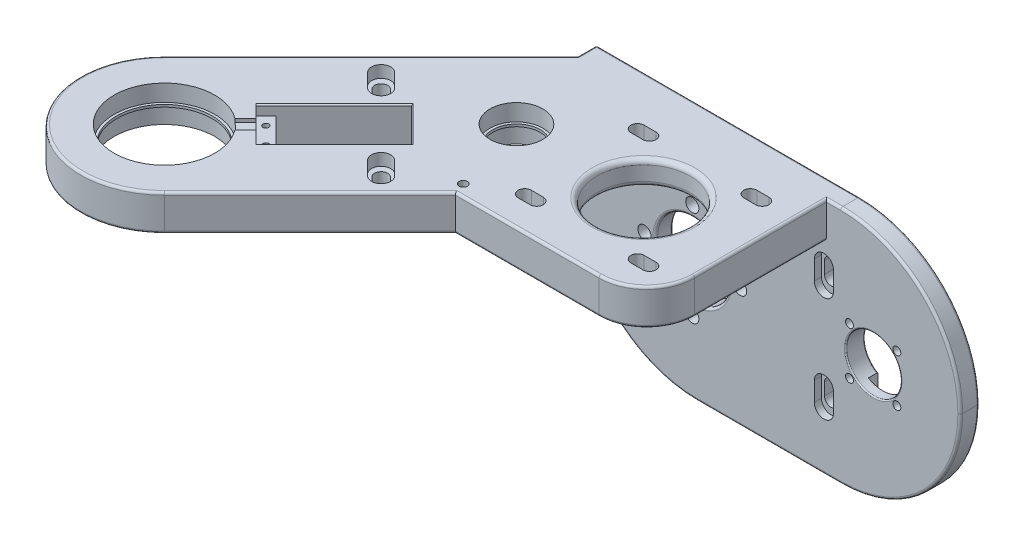
SolidWorks part; units mm, degrees
material "PLA+"
ref_plane "Front Plane" through (0, 0, 0) normal (0, 0, 1) x (1, 0, 0)
ref_plane "Top Plane" through (0, 0, 0) normal (0, 1, 0) x (1, 0, 0)
ref_plane "Right Plane" through (0, 0, 0) normal (1, 0, 0) x (0, 0, -1)
sketch "Sketch1" plane through (0, 0, 0) normal (0, 0, 1) x (1, 0, 0)
  line L0 (-80, 0) -> (80, 0) construction
  line L5 (-80, -50) -> (80, -50)
  line L6 (-80, -50) -> (-80, 50)
  line L7 (-80, 50) -> (80, 50)
  line L8 (80, -50) -> (80, 50)
  line L9 (-80, -50) -> (80, 50) construction
  line L10 (-80, 50) -> (80, -50) construction
  line L12 (33.7005, -9.8995) -> (53.4995, -9.8995) construction
  line L13 (33.7005, -9.8995) -> (33.7005, 9.8995) construction
  line L14 (33.7005, 9.8995) -> (53.4995, 9.8995) construction
  line L15 (53.4995, -9.8995) -> (53.4995, 9.8995) construction
  line L16 (33.7005, -9.8995) -> (53.4995, 9.8995) construction
  line L17 (33.7005, 9.8995) -> (53.4995, -9.8995) construction
  circle A0 centre (-32, 0) radius 15.5
  circle A1 centre (-32, 0) radius 22.5 construction
  circle A4 centre (-32, 0) radius 10 construction
  circle A7 centre (-32, 0) radius 20 construction
  circle A8 centre (-12, 0) radius 2.75
  circle A9 centre (-12, 0) radius 2.75 construction
  circle A10 centre (53.4995, 9.8995) radius 1.65
  circle A11 centre (33.7005, 9.8995) radius 1.65
  circle A12 centre (53.4995, -9.8995) radius 1.65
  circle A13 centre (33.7005, -9.8995) radius 1.65
  circle A17 centre (-32, -20) radius 2.75
  circle A19 centre (-52, 0) radius 2.75
  circle A21 centre (-32, 20) radius 2.75
  circle A22 centre (43.6, 0) radius 14 construction
  circle A23 centre (43.6, 0) radius 11.5
  point P0 (0, 0)
  point P18 (43.6, 0)
  point P40 (-30, 0)
  dimension "D2" = 31
  dimension "D3" = 45
  dimension "D5" = 40
  dimension "D6" = 20
  dimension "D7" = 5.5
  dimension "D8" = 48
  dimension "D9" = 5.5
  dimension "D12" = 75.6
  dimension "D13" = 3.3
  dimension "D14" = 23
  dimension "D11" = 28
  dimension "D1" = 100
  dimension "D10" = 160
extrude "Boss-Extrude1" add sketch "Sketch1" along normal blind 8
sketch "Sketch3" plane through (0, 0, 0) normal (0, 0, -1) x (-1, 0, 0)
  circle A0 centre (32, 0) radius 33
  circle A1 centre (32, 0) radius 22.5 construction
  dimension "D1" = 66
  dimension "D2" = 45
extrude "Cut-Extrude1" cut sketch "Sketch3" against normal blind 0.5
fillet "Fillet1" radius 50 3 edges at (80, -50, 4) (80, 50, 4) (-80, -50, 4)
sketch "Sketch5" plane through (0, 50, 0) normal (0, 1, 0) x (1, 0, 0)
  line L0 (30, -8) -> (-80, -8) construction
  line L1 (23.9949, -8) -> (23.9949, -83)
  line L2 (23.9949, -83) -> (-56.0051, -83)
  line L3 (-56.0051, -83) -> (-116.8282, -143.8232)
  line L4 (-80, -8) -> (-166.3257, -94.3257)
  line L5 (23.9949, -8) -> (-80, -8)
  line L6 (-166.3257, -94.3257) -> (-116.8282, -143.8232) construction
  line L7 (-56.0051, -83) -> (-80, -8) construction
  line L8 (23.9949, -45.5) -> (-68.0025, -45.5) construction
  line L9 (-35.9725, -69.07) -> (-40.9725, -69.07) construction
  line L10 (8.6675, -21.93) -> (-38.4725, -21.93) construction
  line L11 (8.6675, -21.93) -> (8.6675, -69.07) construction
  line L12 (8.6675, -69.07) -> (-38.4725, -69.07) construction
  line L13 (-38.4725, -21.93) -> (-38.4725, -69.07) construction
  line L14 (8.6675, -21.93) -> (-38.4725, -69.07) construction
  line L15 (8.6675, -69.07) -> (-38.4725, -21.93) construction
  line L16 (-35.9725, -71.82) -> (-40.9725, -71.82)
  line L17 (-35.9725, -66.32) -> (-40.9725, -66.32)
  line L18 (11.1675, -69.07) -> (6.1675, -69.07) construction
  line L19 (11.1675, -71.82) -> (6.1675, -71.82)
  line L20 (11.1675, -66.32) -> (6.1675, -66.32)
  line L21 (11.1675, -21.93) -> (6.1675, -21.93) construction
  line L22 (11.1675, -24.68) -> (6.1675, -24.68)
  line L23 (11.1675, -19.18) -> (6.1675, -19.18)
  line L24 (-35.9725, -21.93) -> (-40.9725, -21.93) construction
  line L25 (-35.9725, -24.68) -> (-40.9725, -24.68)
  line L26 (-35.9725, -19.18) -> (-40.9725, -19.18)
  line L27 (-68.0025, -45.5) -> (-141.577, -119.0745) construction
  line L28 (-71.5381, -98.533) -> (-121.0355, -49.0355) construction
  line L29 (-78.6091, -91.4619) -> (-82.1447, -87.9264) construction
  line L30 (-80.5537, -93.4065) -> (-84.0892, -89.871)
  line L31 (-76.6646, -89.5174) -> (-80.2001, -85.9819)
  line L32 (-110.4289, -59.6421) -> (-113.9645, -56.1066) construction
  line L33 (-112.3735, -61.5867) -> (-115.909, -58.0511)
  line L34 (-108.4844, -57.6976) -> (-112.0199, -54.1621)
  line L35 (-125.3135, -88.6689) -> (-111.1714, -102.811)
  line L36 (-111.1714, -102.811) -> (-82.8871, -74.5267)
  line L37 (-82.8871, -74.5267) -> (-97.0293, -60.3846)
  line L38 (-120.3638, -97.8613) -> (-116.8282, -101.3968) construction
  line L39 (-125.3135, -88.6689) -> (-97.0293, -60.3846)
  circle A0 centre (-68.0025, -45.5) radius 10
  circle A1 centre (-14.9025, -45.5) radius 19.5
  arc A3 (-35.9725, -71.82) -> (-35.9725, -66.32) centre (-35.9725, -69.07) ccw
  arc A4 (-40.9725, -66.32) -> (-40.9725, -71.82) centre (-40.9725, -69.07) ccw
  arc A5 (11.1675, -71.82) -> (11.1675, -66.32) centre (11.1675, -69.07) ccw
  arc A6 (6.1675, -66.32) -> (6.1675, -71.82) centre (6.1675, -69.07) ccw
  arc A7 (11.1675, -24.68) -> (11.1675, -19.18) centre (11.1675, -21.93) ccw
  arc A8 (6.1675, -19.18) -> (6.1675, -24.68) centre (6.1675, -21.93) ccw
  arc A9 (-35.9725, -24.68) -> (-35.9725, -19.18) centre (-35.9725, -21.93) ccw
  arc A10 (-40.9725, -19.18) -> (-40.9725, -24.68) centre (-40.9725, -21.93) ccw
  circle A11 centre (-141.577, -119.0745) radius 35 construction
  arc A12 (-116.8282, -143.8232) -> (-166.3257, -94.3257) centre (-141.577, -119.0745) cw
  circle A13 centre (-141.577, -119.0745) radius 20
  arc A16 (-80.5537, -93.4065) -> (-76.6646, -89.5174) centre (-78.6091, -91.4619) ccw
  arc A17 (-80.2001, -85.9819) -> (-84.0892, -89.871) centre (-82.1447, -87.9264) ccw
  arc A18 (-112.3735, -61.5867) -> (-108.4844, -57.6976) centre (-110.4289, -59.6421) ccw
  arc A19 (-112.0199, -54.1621) -> (-115.909, -58.0511) centre (-113.9645, -56.1066) ccw
  circle A20 centre (-116.8282, -101.3968) radius 1.25
  circle A21 centre (-123.8993, -94.3257) radius 1.25
  circle A22 centre (-57.5286, -78.2378) radius 1.75
  point P20 (-38.4725, -69.07)
  point P27 (8.6675, -69.07)
  point P33 (8.6675, -21.93)
  point P40 (-38.4725, -21.93)
  point P54 (-80.3769, -89.6942)
  point P61 (-112.1967, -57.8744)
  point P74 (-89.9582, -67.4557)
  point P75 (-118.2425, -95.7399)
  dimension "D3" = 20
  dimension "D5" = 39
  dimension "D7" = 5
  dimension "D11" = 53.1
  dimension "D4" = 104.05
  dimension "D12" = 40
  dimension "D13" = 40
  dimension "D14" = 5.5
  dimension "D15" = 5
  dimension "D16" = 20
  dimension "D17" = 20
  dimension "D20" = 2.5
  dimension "D23" = 30
  dimension "D24" = 3.5
  dimension "D25" = 5
  dimension "D1" = 135
  dimension "D2" = 70
  dimension "D6" = 47.14
  dimension "D8" = 80
  dimension "D9" = 75
  dimension "D10" = 5.5
  dimension "D18" = 40
  dimension "D19" = 10
  dimension "D21" = 5
  dimension "D22" = 3
extrude "Boss-Extrude2" add sketch "Sketch5" against normal blind 15
fillet "Fillet2" radius 20 1 edges at (23.9949, 42.5, 83)
sketch "Sketch6" plane through (0, 35, 0) normal (0, -1, 0) x (1, 0, 0)
  line L1 (-45.4025, 15) -> (15.5975, 15)
  line L2 (-45.4025, 15) -> (-45.4025, 76)
  line L3 (-45.4025, 76) -> (15.5975, 76)
  line L4 (15.5975, 15) -> (15.5975, 76)
  line L5 (-45.4025, 15) -> (15.5975, 76) construction
  line L6 (-45.4025, 76) -> (15.5975, 15) construction
  circle A0 centre (11.1675, 21.93) radius 4.25 construction
  point P0 (-14.9025, 45.5)
  dimension "D2" = 8.5
  dimension "D1" = 61
extrude "Cut-Extrude2" cut sketch "Sketch6" against normal blind 5
sketch "Sketch7" plane through (0, 50, 0) normal (0, 1, 0) x (1, 0, 0)
  circle A0 centre (-68.0025, -45.5) radius 11.05
  dimension "D1" = 22.1
extrude "Cut-Extrude3" cut sketch "Sketch7" against normal blind 7
sketch "Sketch8" plane through (0, 35, 0) normal (0, -1, 0) x (1, 0, 0)
  circle A0 centre (-68.0025, 45.5) radius 11.05
  dimension "D1" = 22.1
extrude "Cut-Extrude4" cut sketch "Sketch8" against normal blind 7
sketch "Sketch10" plane through (0, 50, 0) normal (0, 1, 0) x (1, 0, 0)
  circle A0 centre (-141.577, -119.0745) radius 21.05
  dimension "D1" = 42.1
extrude "Cut-Extrude5" cut sketch "Sketch10" against normal blind 7
sketch "Sketch11" plane through (0, 35, 0) normal (0, -1, 0) x (1, 0, 0)
  circle A0 centre (-141.577, 119.0745) radius 21.05
  dimension "D1" = 42.1
extrude "Cut-Extrude6" cut sketch "Sketch11" against normal blind 7
sketch "Sketch14" plane through (0, 50, 0) normal (0, 1, 0) x (1, 0, 0)
  line L2 (-76.6646, -93.4065) -> (-84.0892, -85.9819) construction
  line L3 (-84.0892, -85.9819) -> (-108.4844, -61.5867) construction
  line L4 (-108.4844, -61.5867) -> (-115.909, -54.1621) construction
  line L5 (-77.5485, -92.5226) -> (-83.2053, -86.8657) construction
  line L6 (-80.3769, -95.351) -> (-86.0337, -89.6942)
  line L7 (-74.72, -89.6942) -> (-80.3769, -84.0373)
  line L8 (-109.3683, -60.7028) -> (-115.0251, -55.0459) construction
  line L9 (-112.1967, -63.5312) -> (-117.8536, -57.8744)
  line L10 (-106.5398, -57.8744) -> (-112.1967, -52.2175)
  arc A0 (-80.5537, -93.4065) -> (-76.6646, -89.5174) centre (-78.6091, -91.4619) ccw construction
  arc A1 (-80.2001, -85.9819) -> (-84.0892, -89.871) centre (-82.1447, -87.9264) ccw construction
  arc A2 (-112.3735, -61.5867) -> (-108.4844, -57.6976) centre (-110.4289, -59.6421) ccw construction
  arc A3 (-112.0199, -54.1621) -> (-115.909, -58.0511) centre (-113.9645, -56.1066) ccw construction
  arc A4 (-80.3769, -95.351) -> (-74.72, -89.6942) centre (-77.5485, -92.5226) ccw
  arc A5 (-80.3769, -84.0373) -> (-86.0337, -89.6942) centre (-83.2053, -86.8657) ccw
  arc A6 (-112.1967, -63.5312) -> (-106.5398, -57.8744) centre (-109.3683, -60.7028) ccw
  arc A7 (-112.1967, -52.2175) -> (-117.8536, -57.8744) centre (-115.0251, -55.0459) ccw
  point P18 (-80.3769, -89.6942)
  point P25 (-112.1967, -57.8744)
  dimension "D1" = 8
  dimension "D2" = 8
extrude "Cut-Extrude8" cut sketch "Sketch14" against normal blind 5
sketch "Sketch15" plane through (0, 35, 0) normal (0, -1, 0) x (1, 0, 0)
  line L0 (-118.2425, 95.7399) -> (-126.6924, 104.1899) construction
  line L1 (-125.3135, 88.6689) -> (-111.1714, 102.811) construction
  line L2 (-111.1714, 102.811) -> (-115.414, 107.0536)
  line L3 (-115.414, 107.0536) -> (-129.5562, 92.9115)
  line L4 (-125.3135, 88.6689) -> (-129.5562, 92.9115)
  line L5 (-111.1714, 102.811) -> (-125.3135, 88.6689)
  circle A0 centre (-141.577, 119.0745) radius 21.05 construction
  dimension "D1" = 6
extrude "Cut-Extrude10" cut sketch "Sketch15" against normal blind 4
sketch "Sketch16" plane through (0, 50, 0) normal (0, 1, 0) x (1, 0, 0)
  line L0 (-125.3135, -88.6689) -> (-129.5562, -92.9115)
  line L1 (-129.5562, -92.9115) -> (-115.414, -107.0536)
  line L2 (-111.1714, -102.811) -> (-115.414, -107.0536)
  line L3 (-111.1714, -102.811) -> (-125.3135, -88.6689)
  dimension "D1" = 6
extrude "Cut-Extrude11" cut sketch "Sketch16" against normal blind 4.1
sketch "Sketch17" plane through (0, 50, 0) normal (0, 1, 0) x (1, 0, 0)
  line L0 (-122.4851, -99.9826) -> (-127.4349, -104.9323) construction
  line L1 (-129.5562, -92.9115) -> (-115.414, -107.0536) construction
  line L2 (-124.6064, -97.8613) -> (-130.2633, -103.5181)
  line L3 (-129.5562, -92.9115) -> (-115.414, -107.0536) construction
  line L4 (-130.2633, -103.5181) -> (-126.0206, -107.7608)
  line L5 (-126.0206, -107.7608) -> (-120.3638, -102.1039)
  line L6 (-120.3638, -102.1039) -> (-124.6064, -97.8613)
  circle A0 centre (-141.577, -119.0745) radius 20 construction
  dimension "D1" = 8
  dimension "D2" = 3
  dimension "D3" = 3
extrude "Cut-Extrude12" cut sketch "Sketch17" against normal blind 1.5
fillet "Fillet3" radius 1 22 edges at (23.9949, 35, 35.5) (18.1371, 35, 77.1421) (-123.1629, 50, 51.1629) (-166.3257, 50, 143.8232) (-26.0051, 50, 83) (23.9949, 50, 35.5) (-25, 50, 0) (-80, 25, 0) (-65.3553, -35.3553, 0) (0, -50, 0) (65.3553, -35.3553, 0) (-80, 17.5, 8) (-65.3553, -35.3553, 8) (0, -50, 8) (65.3553, -35.3553, 8) (26.9975, 50, 8) (-26.0051, 35, 83) (-80, 50, 4) (-86.4166, 50, 113.4116) (18.1371, 50, 77.1421) (65.3553, 35.3553, 0) (65.3553, 35.3553, 8)
fillet "Fillet4" radius 1 5 edges at (-123.1629, 35, 51.1629) (-166.3257, 35, 143.8232) (-47.5, 0, 0.5) (-16.5, 0, 8) (-85.9166, 35, 112.9116)
fillet "Fillet5" radius 0.5 2 edges at (55.1, 0, 0) (55.1, 0, 8)
fillet "Fillet6" radius 2 2 edges at (-14.9025, 50, 65) (-14.9025, 40, 65)
chamfer "Chamfer1" distance 0.5 angle 45 7 edges at (-122.4851, 35, 99.9826) (-113.2927, 35, 76.6481) (-89.9582, 35, 67.4557) (-99.1506, 35, 90.7902) (-99.1506, 50, 90.7902) (-89.9582, 50, 67.4557) (-113.2927, 50, 76.6481)
fillet "Fillet7" radius 3 4 edges at (15.5975, 37.5, 15) (-45.4025, 37.5, 15) (-45.4025, 37.5, 76) (15.5975, 37.5, 76)
sketch "Sketch18" plane through (0, 0, 0) normal (0, 0, -1) x (-1, 0, 0)
  line L0 (17.5255, -35.3485) -> (-47.2186, -8.8371) construction
  line L1 (-47.2186, 8.8371) -> (17.5255, 35.3485) construction
  line L2 (32, 0) -> (-23, 0) construction
  line L3 (-23, 0) -> (-23, -22) construction
  line L4 (-23, -19.5) -> (-23, -24.5) construction
  line L5 (-20.25, -19.5) -> (-20.25, -24.5)
  line L6 (-25.75, -19.5) -> (-25.75, -24.5)
  line L7 (-23, 19.5) -> (-23, 24.5) construction
  line L8 (-20.25, 19.5) -> (-20.25, 24.5)
  line L9 (-25.75, 19.5) -> (-25.75, 24.5)
  circle A0 centre (32, 0) radius 38.1972 construction
  circle A1 centre (-43.6, 0) radius 9.5493 construction
  arc A2 (-20.25, -19.5) -> (-25.75, -19.5) centre (-23, -19.5) ccw
  arc A3 (-25.75, -24.5) -> (-20.25, -24.5) centre (-23, -24.5) ccw
  arc A4 (-20.25, 19.5) -> (-25.75, 19.5) centre (-23, 19.5) cw
  arc A5 (-25.75, 24.5) -> (-20.25, 24.5) centre (-23, 24.5) cw
  point P15 (-23, -22)
  point P22 (-23, 22)
  dimension "D1" = 76.3944
  dimension "D2" = 19.0986
  dimension "D6" = 2.75
  dimension "D3" = 55
  dimension "D4" = 22
  dimension "D5" = 5
extrude "Cut-Extrude13" cut sketch "Sketch18" against normal through all
sketch "Sketch19" plane through (0, 0, 8) normal (0, 0, 1) x (1, 0, 0)
  line L0 (23, 18) -> (23, 26) construction
  line L1 (19, 18) -> (19, 26)
  line L2 (20.25, 22) -> (25.75, 22) construction
  line L3 (20.25, 19.5) -> (20.25, 24.5) construction
  line L4 (25.75, 24.5) -> (25.75, 19.5) construction
  line L5 (20.25, -22) -> (25.75, -22) construction
  line L6 (20.25, -24.5) -> (20.25, -19.5) construction
  line L7 (25.75, -19.5) -> (25.75, -24.5) construction
  line L8 (27, 18) -> (27, 26)
  line L9 (23, -26) -> (23, -18) construction
  line L10 (19, -26) -> (19, -18)
  line L11 (27, -26) -> (27, -18)
  arc A1 (19, 18) -> (27, 18) centre (23, 18) ccw
  arc A2 (27, 26) -> (19, 26) centre (23, 26) ccw
  arc A3 (19, -26) -> (27, -26) centre (23, -26) ccw
  arc A4 (27, -18) -> (19, -18) centre (23, -18) ccw
  point P3 (23, 22)
  point P21 (23, -22)
  dimension "D1" = 4
  dimension "D2" = 8
extrude "Cut-Extrude14" cut sketch "Sketch19" against normal blind 3
sketch "Sketch20" plane through (0, 0, 0) normal (0, 0, -1) x (-1, 0, 0)
  line L0 (-43.6, 25) -> (-43.6, -25) construction
  line L3 (-37.6, 25) -> (-37.6, -25)
  line L4 (-49.6, 25) -> (-49.6, -25)
  arc A2 (-37.6, 25) -> (-49.6, 25) centre (-43.6, 25) ccw
  arc A3 (-49.6, -25) -> (-37.6, -25) centre (-43.6, -25) ccw
  point P2 (-43.6, 0)
  dimension "D1" = 12
  dimension "D2" = 50
extrude "Cut-Extrude16" cut sketch "Sketch20" against normal blind 4
equation "\"ค\"=8.94921"
